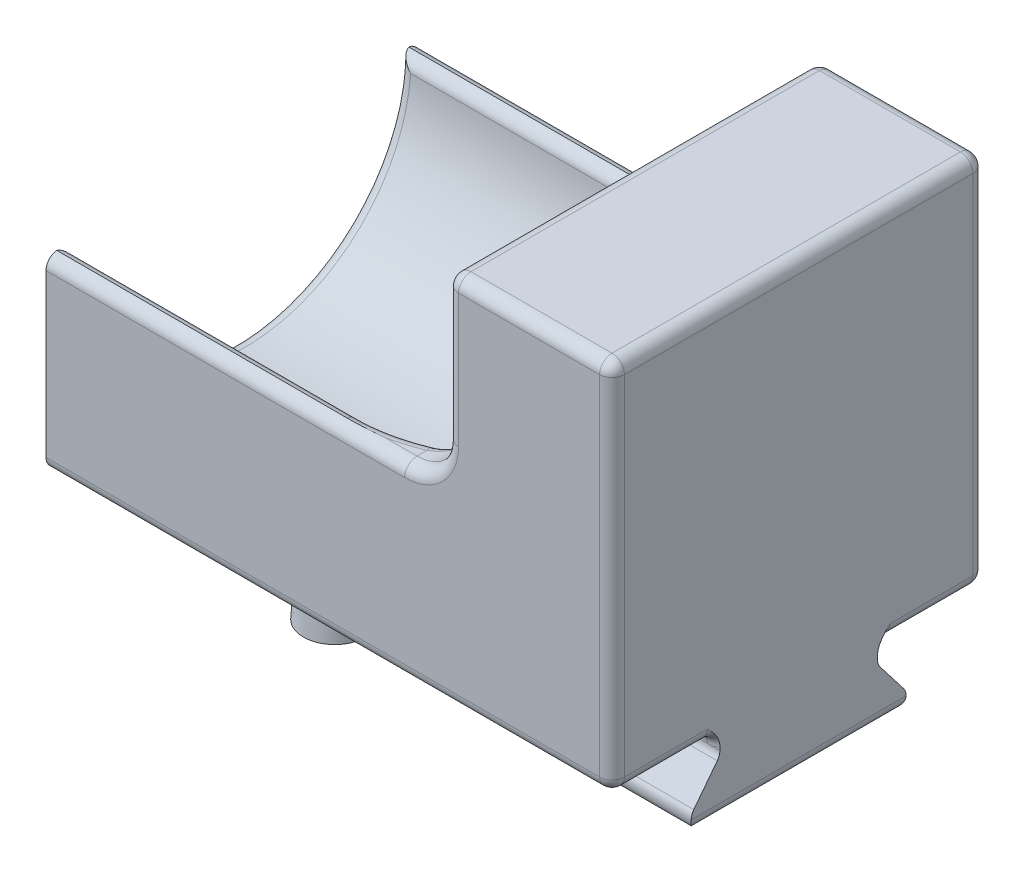
SolidWorks part; units mm, degrees
note: The reader was unsure of these and kept them because the rebuilt part matched: shared geometry of "Sketch4<4>", "Sketch1<2>", "Sketch1<3>".
ref_plane "Front Plane" through (0, 0, 0) normal (0, 0, 1) x (1, 0, 0)
ref_plane "Top Plane" through (0, 0, 0) normal (0, 1, 0) x (1, 0, 0)
ref_plane "Right Plane" through (0, 0, 0) normal (1, 0, 0) x (0, 0, -1)
sketch "Sketch1" plane through (0, 0, 0) normal (1, 0, 0) x (0, 0, -1)
  line L0 (-9.5, 0) -> (9.5, 0)
  line L1 (9.5, 0) -> (14.5, -6.5)
  line L2 (14.5, -6.5) -> (-14.5, -6.5)
  line L3 (-14.5, -6.5) -> (-9.5, 0)
  point P4 (0, 0)
  dimension "D1" = 19
  dimension "D2" = 29
  dimension "D3" = 6.5
extrude "Boss-Extrude1" add sketch "Sketch1" along normal blind 100 and the other way blind 0.1
sketch "Sketch2" plane through (100, 0, 0) normal (1, 0, 0) x (0, 0, -1)
  line L0 (-9.5, 0) -> (-9.5, 2)
  line L1 (-9.5, 2) -> (-22.5, 2)
  line L2 (-22.5, 2) -> (-22.5, 47)
  line L3 (-22.5, 47) -> (22.5, 47)
  line L4 (22.5, 47) -> (22.5, 2)
  line L5 (9.5, 0) -> (9.5, 2)
  line L6 (9.5, 2) -> (22.5, 2)
  line L7 (-9.5, 0) -> (9.5, 0)
  dimension "D1" = 45
  dimension "D2" = 45
  dimension "D3" = 2
extrude "Boss-Extrude2" add sketch "Sketch2" against normal blind 20
sketch "Sketch4" plane through (0, 0, 0) normal (0, 0, 1) x (1, 0, 0)
  line L0 (66.7712, 44.5) -> (66.7712, 4.5)
  line L1 (80, 24.5) -> (66.7712, 24.5) construction
  line L2 (80, 47) -> (80, 2) construction
  line L3 (80, 39.5) -> (80, 9.5) construction
  line L4 (80, 2) -> (80, 0) construction
  arc A0 (66.7712, 4.5) -> (66.7712, 44.5) centre (66.7712, 24.5) ccw
  dimension "D1" = 40
  dimension "D2" = 30
revolve "Cut-Revolve5" cut sketch "Sketch4" angle 360 about L0
sketch "Sketch6" plane through (80, 0, 0) normal (-1, 0, 0) x (0, 0, 1)
  line L1 (-15, 24.5) -> (-22.5, 24.5)
  line L3 (-22.5, 2) -> (-22.5, 47) construction
  line L4 (-22.5, 24.5) -> (-22.5, 2)
  line L5 (-22.5, 2) -> (-9.5, 2)
  line L6 (-9.5, 2) -> (-9.5, 0)
  line L7 (-9.5, 0) -> (9.5, 0)
  line L8 (9.5, 0) -> (9.5, 2)
  line L9 (22.5, 2) -> (9.5, 2) construction
  line L10 (9.5, 2) -> (22.5, 2)
  line L11 (22.5, 2) -> (22.5, 24.5)
  line L12 (0, 4.5) -> (0, 44.5) construction
  line L13 (15, 24.5) -> (22.5, 24.5)
  line L14 (22.5, 47) -> (22.5, 2) construction
  circle A0 centre (0, 24.5) radius 15 construction
  arc A1 (-15, 24.5) -> (15, 24.5) centre (0, 24.5) ccw
extrude "Boss-Extrude6" add sketch "Sketch6" along normal up to vertex (13.2288 mm away) up to point (66.7712, 4.5, 0)
revolve "Cut-Revolve6" cut sketch "Sketch4<4>" angle 360 about L0
sketch "Sketch4<4>" plane through (0, 0, 0) normal (0, 0, 1) x (1, 0, 0) same geometry as "Sketch4"
sketch "Sketch11" plane through (66.7712, 0, 0) normal (-1, 0, 0) x (0, 0, 1)
  line L0 (-22.5, 24.5) -> (-22.5, 2)
  line L1 (-22.5, 2) -> (-9.5, 2)
  line L2 (-9.5, 2) -> (-9.5, 0)
  line L3 (-9.5, 0) -> (9.5, 0)
  line L4 (9.5, 0) -> (9.5, 2)
  line L5 (9.5, 0) -> (9.5, 2) construction
  line L6 (9.5, 2) -> (22.5, 2)
  line L7 (22.5, 2) -> (22.5, 24.5)
  line L8 (22.5, 24.5) -> (20, 24.5)
  line L9 (-20, 24.5) -> (-22.5, 24.5)
  line L10 (0, 4.5) -> (0, 44.5) construction
  arc A0 (-20, 24.5) -> (20, 24.5) centre (0, 24.5) ccw
extrude "Boss-Extrude7" add sketch "Sketch11" along normal blind 35
fillet "Fillet5" radius 5 2 edges at (80, 24.5, 18.75) (80, 24.5, -18.75)
fillet "Fillet6" radius 1.5 11 edges at (80, 38.25, 22.5) (78.5355, 25.9645, 22.5) (80, 38.25, -22.5) (78.5355, 25.9645, -22.5) (78.3435, 25.7823, 16.2616) (80, 39.5, 0) (78.8686, 26.3324, -15.8207) (70.9799, 24.5, 19.5522) (53.3856, 24.5, 22.5) (53.3856, 24.5, -22.5) (70.9799, 24.5, -19.5522)
fillet "Fillet7" radius 1.5 1 edges at (31.7712, 4.5, 0)
fillet "Fillet8" radius 1.5 12 edges at (80.4393, 47, -22.0607) (90.75, 47, -22.5) (100, 47, 0) (90.75, 47, 22.5) (80.4393, 47, 22.0607) (80, 47, 0) (65.8856, 2, 22.5) (65.8856, 2, -22.5) (100, 2, 16) (100, 2, -16) (100, 24.5, -22.5) (100, 24.5, 22.5)
sketch "Sketch13" plane through (0, -6.5, 0) normal (0, -1, 0) x (1, 0, 0)
  line L0 (0, 0) -> (47.8167, 0) construction
  circle A1 centre (44.0667, 0) radius 3.75
  dimension "D2" = 7.5
  dimension "D1" = 47.8167
extrude "Boss-Extrude8" add sketch "Sketch13" along normal blind 6 draft 3 contours A1
sketch "Sketch14" plane through (0, -12.5, 0) normal (0, -1, 0) x (1, 0, 0)
  circle A0 centre (44.0667, 0) radius 3.4356
extrude "Boss-Extrude9" add sketch "Sketch14" along normal blind 6 draft 3 draft outward yes
fillet "Fillet9" radius 1.5 10 edges at (49.95, -6.5, 14.5) (100, -6.5, 0) (-0.1, -6.5, 0) (49.95, -6.5, -14.5) (99.5607, 2.4393, -9.5) (99.5607, 2.4393, 9.5) (65.1356, 2, -9.5) (65.1356, 2, 9.5) (65.8856, 0, 9.5) (65.8856, 0, -9.5)
fillet "Fillet10" radius 3 1 edges at (44.0667, -6.5, -3.75)
ref_plane "Plane1" through (0, 0, 0) normal (0, 0, 1) x (1, 0, 0)
ref_plane "Plane2" through (0, 0, 0) normal (0, 0, 1) x (1, 0, 0)
sketch "Sketch21" plane through (0, 0, 0) normal (0, 0, 1) x (1, 0, 0)
  line L0 (67.753, 0) -> (67.753, -6.5) construction
  line L1 (-0.1, 0) -> (67.753, 0) construction
  line L2 (67.753, -6.5) -> (82.0989, -6.5)
  line L3 (81.2337, -1.5934) -> (67.753, -6.5)
  line L4 (368.8372, -25.2342) -> (368.8372, -31.7342) construction
  line L5 (297.6372, -25.2342) -> (368.8372, -25.2342) construction
  line L6 (368.8372, -31.7342) -> (379.3553, -31.7342)
  line L7 (377.7372, -26.1288) -> (368.8372, -31.7342)
  line L8 (-0.1, -4.0854) -> (-0.1, 0) construction
  line L9 (37.4699, -6.5) -> (50.6636, -6.5) construction
  arc A0 (81.2337, -1.5934) -> (82.0989, -6.5) centre (67.753, -6.5) cw
  arc A1 (377.7372, -26.1288) -> (379.3553, -31.7342) centre (368.8372, -31.7342) cw
  dimension "D3" = 20
  dimension "D1" = 67.853
  dimension "D2" = 14.3459
  dimension "D4" = 6.5
extrude "Cut-Extrude1" cut sketch "Sketch21" against normal blind 6 and the other way blind 6
extrude "Cut-Extrude2" cut sketch "Sketch1<2>" along normal up to surface (31.7712 mm away) up to face at (31.7712, 5.5551, 0)
sketch "Sketch1<2>" plane through (0, 0, 0) normal (1, 0, 0) x (0, 0, -1) same geometry as "Sketch1"
extrude "Cut-Extrude3" cut sketch "Sketch1<3>" against normal blind 19
sketch "Sketch1<3>" plane through (0, 0, 0) normal (1, 0, 0) x (0, 0, -1) same geometry as "Sketch1"
